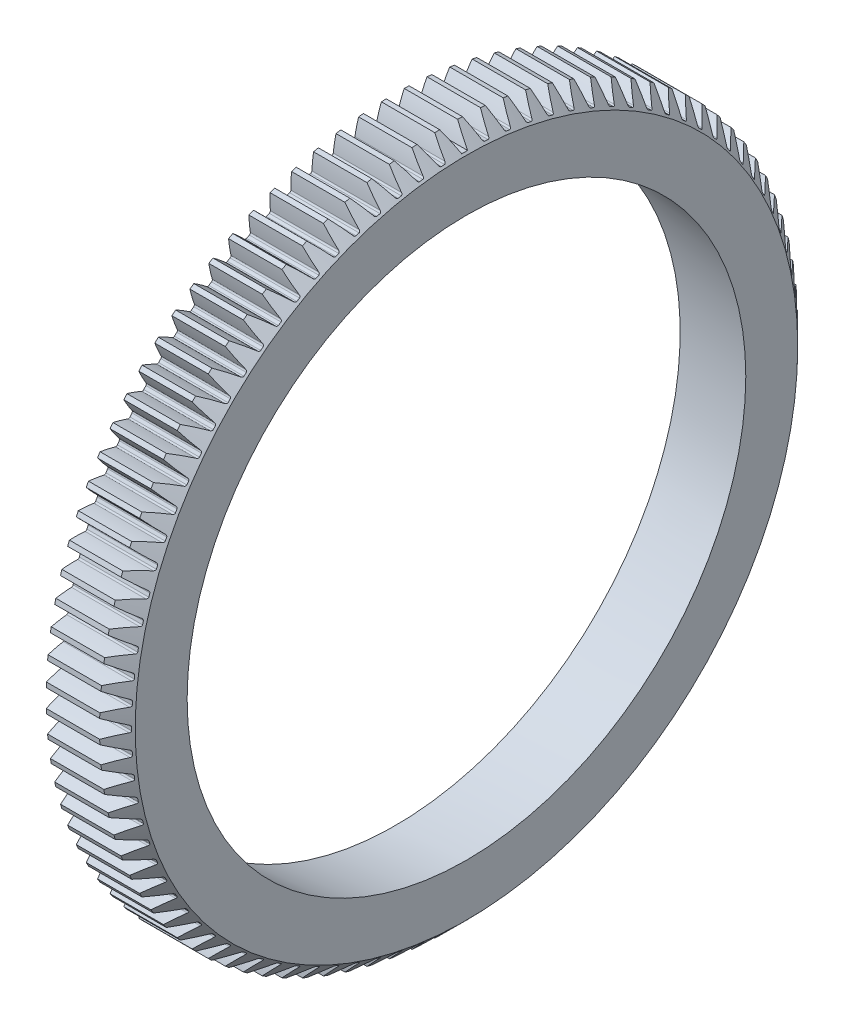
SolidWorks part; units mm, degrees
ref_plane "Plane1" through (0, 0, 0) normal (0, 0, 1) x (1, 0, 0)
ref_plane "Plane2" through (0, 0, 0) normal (0, 1, 0) x (1, 0, 0)
ref_plane "Plane3" through (0, 0, 0) normal (1, 0, 0) x (0, 0, -1)
sketch "HoldingSke" plane through (0, 0, 0) normal (0, 1, 0) x (1, 0, 0)
  line L0 (0, 0) -> (-0.0523, -0.4973)
  line L1 (-15, 0) -> (100, 0) construction
  line L2 (0, 0) -> (-2.1039, 2.3779)
  line L3 (0, 0) -> (-11.863, 4.5341)
  line L4 (0, 0) -> (-0.9027, 8.5887)
  line L5 (0, 0) -> (-46.8476, -17.4728)
  line L6 (0, 0) -> (-9.9476, -6.7116)
  line L7 (-2.1039, 2.3779) -> (8.6586, 51.2059)
  line L8 (-76.2, 54.61) -> (-66.8, 54.61)
  line L9 (-71.009, 38.7566) -> (-53.1078, 45.2721)
  line L10 (-76.2, 71.12) -> (104.1128, 71.12)
  line L11 (0, 0) -> (-12, 0)
  line L12 (-76.2, 101.6) -> (-76.133, 101.6)
  line L13 (24.9733, 27.94) -> (52.9518, 28.4284)
  line L14 (24.9733, 27.94) -> (24.9743, 27.94)
  line L15 (24.9733, 27.94) -> (100.4006, 29.5858)
  line L16 (-63.627, -2) -> (-12.827, -2)
  circle A0 centre (0, 0) radius 77.5
  circle A1 centre (0, 0) radius 37.5
  circle A2 centre (0, 0) radius 37.5
  circle A3 centre (0, 0) radius 77.5
  dimension "Num_teeth" = 96
  dimension "Pitch_radius" = 180.3128
  dimension "Width" = 12
sketch "BasProSke" plane through (0, 0, 0) normal (0, 1, 0) x (1, 0, 0)
  line L0 (-10, 0) -> (60, 0) construction
  line L1 (0, 0) -> (0, 98)
  line L2 (0, 0) -> (20, 0)
  line L3 (20, 0) -> (20, 98)
  line L4 (20, 98) -> (0, 98)
  dimension "Thickness" = 20
  dimension "Diameter" = 196
revolve "Base-Revolve" add sketch "BasProSke" angle 360 about L0
sketch "TooCutSke" plane through (0, 0, 0) normal (1, 0, 0) x (0, 0, -1)
  line L1 (0, 0) -> (0, 107) construction
  line L2 (0, 0) -> (-1.688, 95.9852) construction
  line L3 (0, 0) -> (-6.2813, 191.8752) construction
  line L4 (-1.688, 95.9852) -> (-3.1407, 95.9376) construction
  arc A0 (0.8163, 93.4954) -> (-0.8163, 93.4954) centre (0, 0) ccw
  arc A1 (2.5355, 97.9926) -> (-2.5355, 97.9926) centre (0, 0) ccw
  circle A2 centre (0, 0) radius 96 construction
  circle A3 centre (0, 0) radius 90.2105 construction
  arc A4 (-0.8163, 93.4954) -> (-2.5355, 97.9926) centre (-37.4737, 82.0589) ccw
  arc A5 (2.5355, 97.9926) -> (0.8163, 93.4954) centre (37.4737, 82.0589) ccw
extrude "ToothCut" cut sketch "TooCutSke" along normal through all
fillet "Breaks" [suppressed] radius 0.04 tangent propagation no
fillet "RootFillets" [suppressed] radius 0.501
pattern_circular "TeethCuts" count 96 every 3.75 about axis through (-10, 0, 0) along (1, 0, 0) of "ToothCut", "RootFillets", "Breaks"
sketch "HubNeaOneSke" plane through (0, 0, 0) normal (-1, 0, 0) x (0, 0, 1)
  circle A0 centre (0, 0) radius 37.5
  dimension "Diameter" = 75
extrude "HubNearOne" [suppressed] add sketch "HubNeaOneSke" along normal blind 30.0001
sketch "HubNeaBotSke" plane through (0, 0, 0) normal (-1, 0, 0) x (0, 0, 1)
  circle A0 centre (0, 0) radius 37.5
  dimension "Diameter" = 75
extrude "HubNearBoth" [suppressed] add sketch "HubNeaBotSke" along normal blind 15
ref_plane "FarPln" through (20, 0, 0) normal (1, 0, 0) x (0, 0, -1)
sketch "HubFarSke" plane through (20, 0, 0) normal (1, 0, 0) x (0, 0, -1)
  circle A0 centre (0, 0) radius 37.5
  dimension "Diameter" = 75
extrude "HubFar" [suppressed] add sketch "HubFarSke" along normal blind 15
sketch "BorSke" plane through (0, 0, 0) normal (1, 0, 0) x (0, 0, -1)
  circle A0 centre (0, 0) radius 77.5
  dimension "Diameter" = 155
extrude "Bore" cut sketch "BorSke" along normal mid plane 100.0001
sketch "KeySke" plane through (0, 0, 0) normal (1, 0, 0) x (0, 0, -1)
  line L0 (-20, 0) -> (-20, 86.9)
  line L1 (-20, 86.9) -> (20, 86.9)
  line L2 (20, 86.9) -> (20, 0)
  line L3 (0, 0) -> (0, 34) construction
  line L4 (-20, 0) -> (20, 0)
  dimension "Width" = 40
extrude "Keyway" [suppressed] cut sketch "KeySke" along normal mid plane 100.0001
pattern_circular "Keyway2" [suppressed] count 2 every 90 about axis through (-10, 0, 0) along (1, 0, 0) reverse direction yes
fillet "Скругление1" radius 0.5 190 edges at (10, 93.2419, -6.9294) (10, 93.3486, -5.3003) (10, 92.589, -13.0129) (10, 92.8021, -11.3943) (10, 91.5397, -19.0407) (10, 91.8582, -17.4394) (10, 90.0984, -24.9869) (10, 90.5209, -23.4099) (10, 88.2713, -30.8261) (10, 88.796, -29.2801) (10, 86.0661, -36.5333) (10, 86.6909, -35.025) (10, 83.4925, -42.0841) (10, 84.2145, -40.6199) (10, 80.5613, -47.4547) (10, 81.3776, -46.0408) (10, 77.2851, -52.622) (10, 78.1921, -51.2646) (10, 73.678, -57.564) (10, 74.6719, -56.2688) (10, 69.7554, -62.2596) (10, 70.8318, -61.0321) (10, 65.534, -66.6885) (10, 66.6885, -65.534) (10, 61.0321, -70.8318) (10, 62.2596, -69.7554) (10, 56.2688, -74.6719) (10, 57.564, -73.678) (10, 51.2646, -78.1921) (10, 52.622, -77.2851) (10, 46.0408, -81.3776) (10, 47.4547, -80.5613) (10, 40.6199, -84.2145) (10, 42.0841, -83.4925) (10, 35.025, -86.6909) (10, 36.5333, -86.0661) (10, 29.2801, -88.796) (10, 30.8261, -88.2713) (10, 23.4099, -90.5209) (10, 24.9869, -90.0984) (10, 17.4394, -91.8582) (10, 19.0407, -91.5397) (10, 11.3943, -92.8021) (10, 13.0129, -92.589) (10, 5.3003, -93.3486) (10, 6.9294, -93.2419) (10, -0.8163, -93.4954) (10, 0.8163, -93.4954) (10, -6.9294, -93.2419) (10, -5.3003, -93.3486) (10, -13.0129, -92.589) (10, -11.3943, -92.8021) (10, -19.0407, -91.5397) (10, -17.4394, -91.8582) (10, -24.9869, -90.0984) (10, -23.4099, -90.5209) (10, -30.8261, -88.2713) (10, -29.2801, -88.796) (10, -36.5333, -86.0661) (10, -35.025, -86.6909) (10, -42.0841, -83.4925) (10, -40.6199, -84.2145) (10, -47.4547, -80.5613) (10, -46.0408, -81.3776) (10, -52.622, -77.2851) (10, -51.2646, -78.1921) (10, -57.564, -73.678) (10, -56.2688, -74.6719) (10, -62.2596, -69.7554) (10, -61.0321, -70.8318) (10, -66.6885, -65.534) (10, -65.534, -66.6885) (10, -70.8318, -61.0321) (10, -69.7554, -62.2596) (10, -74.6719, -56.2688) (10, -73.678, -57.564) (10, -78.1921, -51.2646) (10, -77.2851, -52.622) (10, -81.3776, -46.0408) (10, -80.5613, -47.4547) (10, -84.2145, -40.6199) (10, -83.4925, -42.0841) (10, -86.6909, -35.025) (10, -86.0661, -36.5333) (10, -88.796, -29.2801) (10, -88.2713, -30.8261) (10, -90.5209, -23.4099) (10, -90.0984, -24.9869) (10, -91.8582, -17.4394) (10, -91.5397, -19.0407) (10, -92.8021, -11.3943) (10, -92.589, -13.0129) (10, -93.3486, -5.3003) (10, -93.2419, -6.9294) (10, -93.4954, 0.8163) (10, -93.4954, -0.8163) (10, -93.2419, 6.9294) (10, -93.3486, 5.3003) (10, -92.589, 13.0129) (10, -92.8021, 11.3943) (10, -91.5397, 19.0407) (10, -91.8582, 17.4394) (10, -90.0984, 24.9869) (10, -90.5209, 23.4099) (10, -88.2713, 30.8261) (10, -88.796, 29.2801) (10, -86.0661, 36.5333) (10, -86.6909, 35.025) (10, -83.4925, 42.0841) (10, -84.2145, 40.6199) (10, -80.5613, 47.4547) (10, -81.3776, 46.0408) (10, -77.2851, 52.622) (10, -78.1921, 51.2646) (10, -73.678, 57.564) (10, -74.6719, 56.2688) (10, -69.7554, 62.2596) (10, -70.8318, 61.0321) (10, -65.534, 66.6885) (10, -66.6885, 65.534) (10, -61.0321, 70.8318) (10, -62.2596, 69.7554) (10, -56.2688, 74.6719) (10, -57.564, 73.678) (10, -51.2646, 78.1921) (10, -52.622, 77.2851) (10, -46.0408, 81.3776) (10, -47.4547, 80.5613) (10, -40.6199, 84.2145) (10, -42.0841, 83.4925) (10, -35.025, 86.6909) (10, -36.5333, 86.0661) (10, -29.2801, 88.796) (10, -30.8261, 88.2713) (10, -23.4099, 90.5209) (10, -24.9869, 90.0984) (10, -17.4394, 91.8582) (10, -19.0407, 91.5397) (10, -11.3943, 92.8021) (10, -13.0129, 92.589) (10, -5.3003, 93.3486) (10, -6.9294, 93.2419) (10, 0.8163, 93.4954) (10, 6.9294, 93.2419) (10, 5.3003, 93.3486) (10, 13.0129, 92.589) (10, 11.3943, 92.8021) (10, 19.0407, 91.5397) (10, 17.4394, 91.8582) (10, 24.9869, 90.0984) (10, 23.4099, 90.5209) (10, 30.8261, 88.2713) (10, 29.2801, 88.796) (10, 36.5333, 86.0661) (10, 35.025, 86.6909) (10, 42.0841, 83.4925) (10, 40.6199, 84.2145) (10, 47.4547, 80.5613) (10, 46.0408, 81.3776) (10, 52.622, 77.2851) (10, 51.2646, 78.1921) (10, 57.564, 73.678) (10, 56.2688, 74.6719) (10, 62.2596, 69.7554) (10, 61.0321, 70.8318) (10, 66.6885, 65.534) (10, 65.534, 66.6885) (10, 70.8318, 61.0321) (10, 69.7554, 62.2596) (10, 74.6719, 56.2688) (10, 73.678, 57.564) (10, 78.1921, 51.2646) (10, 77.2851, 52.622) (10, 81.3776, 46.0408) (10, 80.5613, 47.4547) (10, 84.2145, 40.6199) (10, 83.4925, 42.0841) (10, 86.6909, 35.025) (10, 86.0661, 36.5333) (10, 88.796, 29.2801) (10, 88.2713, 30.8261) (10, 90.5209, 23.4099) (10, 90.0984, 24.9869) (10, 91.8582, 17.4394) (10, 91.5397, 19.0407) (10, 92.8021, 11.3943) (10, 92.589, 13.0129) (10, 93.3486, 5.3003) (10, 93.2419, 6.9294) (10, -0.8163, 93.4954)
sketch "Эскиз1" plane through (0, 0, 0) normal (-1, 0, 0) x (0, 0, 1)
  circle A0 centre (0, 0) radius 80
  dimension "D1" = 160
extrude "Вырез-Вытянуть1" cut sketch "Эскиз1" against normal through all draft 4.53
sketch "Эскиз2" plane through (20, 0, 0) normal (1, 0, 0) x (0, 0, -1)
  circle A0 centre (0, 0) radius 93
  dimension "D1" = 186
extrude "Вырез-Вытянуть2" cut sketch "Эскиз2" against normal blind 10 draft 45 flip side to cut
equation "' \"Module@HoldingSke\" = 6.35"
equation "' \"Num_teeth@HoldingSke\" = 12"
equation "' \"Ap@HoldingSke\" =  20"
equation "' \"Ap@HoldingSke\" = 20"
equation "' \"Width@HoldingSke\" = 0.5 * 25.4"
equation "' \"Hub_dia@HoldingSke\"= 1 * 25.4"
equation "' \"Hub_dia@HoldingSke\" = 1 * 25.4"
equation "' \"Overall_len@HoldingSke\" = 1.0 * 25.4"
equation "' \"Bore@HoldingSke\" = 0.75 * 25.4"
equation "' \"T_dim@HoldingSke\" = 0.1 * 25.4"
equation "' \"Width@KeySke\" = 0.25 * 25.4"
equation "' \"Show_teeth@HoldingSke\" = 13"
equation "' \"Backlash@HoldingSke\" = 0.009 * 25.4"
equation "' \"Addendum_fac@HoldingSke\" = 1.0"
equation "' \"Dedendum_fac@HoldingSke\" = 1.25"
equation "' \"Dedendum_add@HoldingSke\" = 0.00005 * 25.4"
equation "' \"Clearance_fac@HoldingSke\" = 0.25"
equation "\"Pitch@HoldingSke\" = 1 / \"Module@HoldingSke\""
equation "\"Overcut_dia@TooCutSke\" = (\"Num_teeth@HoldingSke\" + 2 * \"Addendum_fac@HoldingSke\") / \"Pitch@HoldingSke\" + 0.002 * 25.4"
equation "\"Pitch_dia@TooCutSke\" = \"Num_teeth@HoldingSke\" / \"Pitch@HoldingSke\""
equation "\"Base_dia@TooCutSke\" = \"Num_teeth@HoldingSke\" / \"Pitch@HoldingSke\" * cos((\"Ap@HoldingSke\"  * 3.14159265 / 180))"
equation "\"Root_dia@TooCutSke\" = (\"Num_teeth@HoldingSke\" + 2) / \"Pitch@HoldingSke\" - 2 * (\"Addendum_fac@HoldingSke\" + \"Dedendum_fac@HoldingSke\") / \"Pitch@HoldingSke\" - \"Dedendum_add@HoldingSke\" * 2"
equation "\"Half_ang@TooCutSke\" = 180 / \"Num_teeth@HoldingSke\""
equation "\"Half_CT@TooCutSke\" = \"Num_teeth@HoldingSke\" / \"Pitch@HoldingSke\" * sin((3.14159265 / 2 / \"Num_teeth@HoldingSke\")) / 2 - 7 * \"Backlash@HoldingSke\" / 4"
equation "\"Flank_rad@TooCutSke\" = \"Num_teeth@HoldingSke\" / \"Pitch@HoldingSke\" / 5"
equation "\"Radius@RootFillets\" = \"Clearance_fac@HoldingSke\" / \"Pitch@HoldingSke\" + \"Dedendum_add@HoldingSke\""
equation "\"Break_rad@Breaks\" = 0.02 / \"Pitch@HoldingSke\""
equation "\"Thickness@HoldingSke\" = \"Width@HoldingSke\""
equation "\"OAL@HoldingSke\" = \"Thickness@HoldingSke\""
equation "\"MHD@HoldingSke\" = (\"Num_teeth@HoldingSke\" + 2) / \"Pitch@HoldingSke\" - 2 * (\"Addendum_fac@HoldingSke\" + \"Dedendum_fac@HoldingSke\")  / \"Pitch@HoldingSke\" - \"Dedendum_add@HoldingSke\" * 2"
equation "\"MBD@HoldingSke\" = (\"Num_teeth@HoldingSke\" + 2) / \"Pitch@HoldingSke\" - 2 * (\"Addendum_fac@HoldingSke\" + \"Dedendum_fac@HoldingSke\")  / \"Pitch@HoldingSke\" - \"Dedendum_add@HoldingSke\" * 2 - 0.002 * 25.4"
equation "\"MHD@HoldingSke\" = ((sgn( \"MHD@HoldingSke\" - \"Hub_dia@HoldingSke\" )-1)*( \"MHD@HoldingSke\" - \"Hub_dia@HoldingSke\" ))/-2+ \"Hub_dia@HoldingSke\""
equation "\"MBD@HoldingSke\" = ((sgn( \"MBD@HoldingSke\" - \"Bore@HoldingSke\" )-1)*( \"MBD@HoldingSke\" - \"Bore@HoldingSke\" ))/-2+ \"Bore@HoldingSke\""
equation "\"OAL@HoldingSke\" = ((sgn( \"OAL@HoldingSke\" - \"Overall_len@HoldingSke\" )+1)*( \"OAL@HoldingSke\" - \"Overall_len@HoldingSke\" ))/2 + \"Overall_len@HoldingSke\" + 0.000002 * 25.4"
equation "\"Num_teeth@TeethCuts\" = int( \"Show_teeth@HoldingSke\" ) + 1"
equation "\"Num_teeth@TeethCuts\" = ((sgn( \"Num_teeth@TeethCuts\" - \"Num_teeth@HoldingSke\" )-1)*( \"Num_teeth@TeethCuts\" - \"Num_teeth@HoldingSke\" ))/-2+ \"Num_teeth@HoldingSke\""
equation "\"Num_teeth@TeethCuts\" = ((sgn( \"Num_teeth@TeethCuts\" - 2.0)+1)*( \"Num_teeth@TeethCuts\" - 2.0))/2 +2.0"
equation "\"Angle@TeethCuts\" = 360.0 / \"Num_teeth@HoldingSke\""
equation "\"Diameter@BasProSke\" = (\"Num_teeth@HoldingSke\" + 2 * \"Addendum_fac@HoldingSke\") / \"Pitch@HoldingSke\""
equation "' \"Fillet_rad@BasProSke\" =  \"Thickness@HoldingSke\" * 0.05"
equation "' \"Fillet_rad@BasProSke\" = \"Thickness@HoldingSke\" * 0.05"
equation "\"MHD@HoldingSke\" = ((sgn( \"MHD@HoldingSke\" - \"Root_dia@TooCutSke\" )-1)*( \"MHD@HoldingSke\" - \"Root_dia@TooCutSke\" ))/-2+ \"Root_dia@TooCutSke\""
equation "\"Diameter@HubNeaOneSke\" = \"MHD@HoldingSke\""
equation "\"Length@HubNearOne\" = \"OAL@HoldingSke\" - \"Thickness@BasProSke\""
equation "\"Diameter@HubNeaBotSke\" = \"MHD@HoldingSke\""
equation "\"Length@HubNearBoth\" = ( \"OAL@HoldingSke\" - \"Thickness@BasProSke\" ) / 2.0"
equation "\"Thickness@FarPln\" = \"Thickness@BasProSke\""
equation "\"Diameter@HubFarSke\" = \"MHD@HoldingSke\""
equation "\"Length@HubFar\" = ( \"OAL@HoldingSke\" - \"Thickness@BasProSke\" ) / 2.0"
equation "\"Diameter@BorSke\" = \"MBD@HoldingSke\""
equation "\"D1@Bore\" = \"OAL@HoldingSke\" * 2.0"
equation "\"D1@Keyway\" = \"OAL@HoldingSke\" * 2.0"
equation "\"Offset@KeySke\" = \"T_dim@HoldingSke\" + \"MBD@HoldingSke\" / 2.0"
